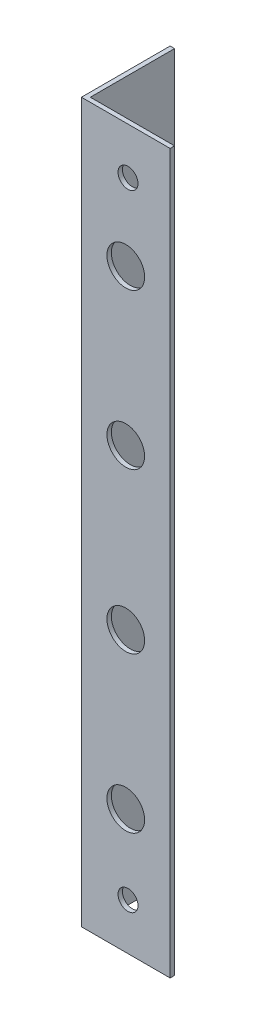
SolidWorks part; units mm, degrees
material "1060 Сплав"
ref_plane "Спереди" through (0, 0, 0) normal (0, 0, 1) x (1, 0, 0)
ref_plane "Сверху" through (0, 0, 0) normal (0, 1, 0) x (1, 0, 0)
ref_plane "Справа" through (0, 0, 0) normal (1, 0, 0) x (0, 0, -1)
sketch "Эскиз1" plane through (0, 0, 0) normal (0, 1, 0) x (1, 0, 0)
  line L0 (0, 0) -> (0, 20)
  line L1 (0, 20) -> (1, 20)
  line L2 (1, 20) -> (1, 1)
  line L3 (1, 1) -> (20, 1)
  line L4 (20, 1) -> (20, 0)
  line L5 (20, 0) -> (0, 0)
  dimension "D1" = 1
  dimension "D2" = 20
extrude "Бобышка-Вытянуть1" add sketch "Эскиз1" along normal blind 162
sketch "Эскиз2" plane through (0, 0, 0) normal (0, 0, 1) x (1, 0, 0)
  line L0 (10, 162) -> (10, 0) construction
  line L1 (0, 162) -> (20, 162) construction
  line L2 (0, 0) -> (20, 0) construction
  line L3 (20, 81) -> (0, 81) construction
  line L4 (20, 162) -> (20, 0) construction
  line L5 (0, 162) -> (0, 0) construction
  circle A0 centre (10, 134) radius 4.25
  circle A1 centre (10, 99) radius 4.25
  circle A2 centre (10, 63) radius 4.25
  circle A3 centre (10, 28) radius 4.25
  dimension "D1" = 8.5
  dimension "D2" = 8.5
  dimension "D3" = 8.5
  dimension "D4" = 8.5
  dimension "D6" = 35
  dimension "D7" = 35
  dimension "D8" = 28
  dimension "D9" = 36
  dimension "D5" = 28
extrude "Вырез-Вытянуть1" cut sketch "Эскиз2" against normal through all
sketch "Эскиз3" plane through (0, 0, -1) normal (0, 0, -1) x (-1, 0, 0)
  circle A0 centre (-10.5, 10.5) radius 2.25 construction
  circle A1 centre (-10.5, 10.5) radius 2.25
  circle A2 centre (-10.5, 151.5) radius 2.25 construction
  circle A3 centre (-10.5, 151.5) radius 2.25
extrude "Вырез-Вытянуть2" cut sketch "Эскиз3" against normal through all
